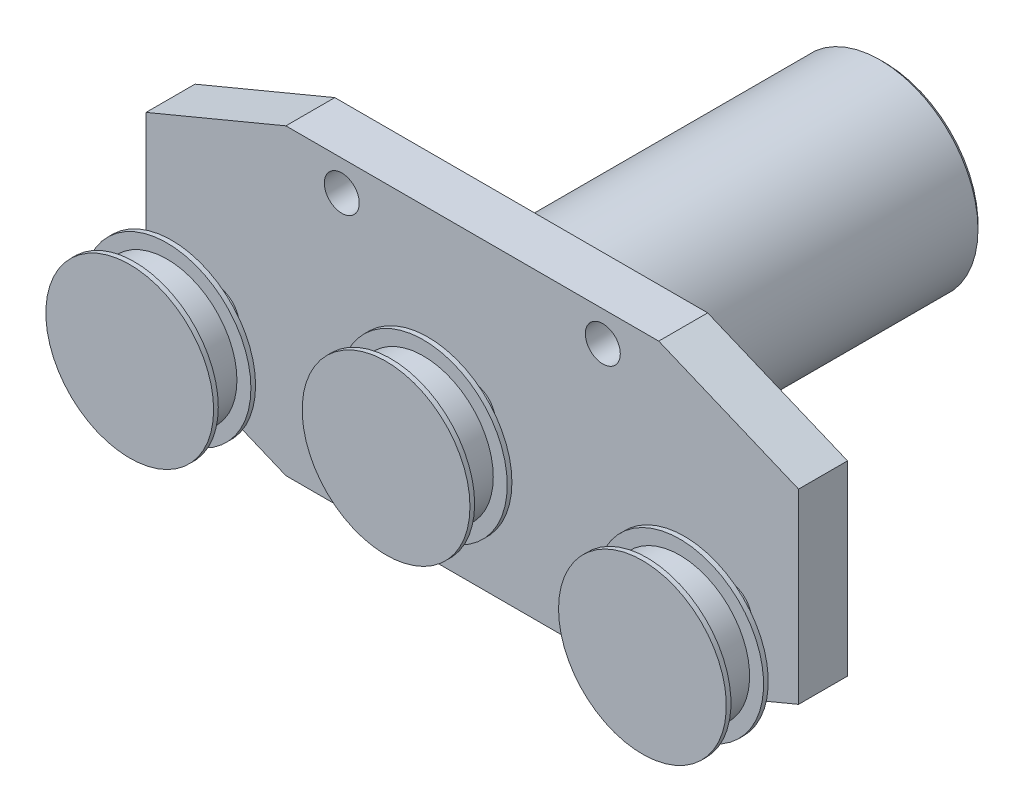
SolidWorks part; units mm, degrees
ref_plane "Front Plane" through (0, 0, 0) normal (0, 0, 1) x (1, 0, 0)
ref_plane "Top Plane" through (0, 0, 0) normal (0, 1, 0) x (1, 0, 0)
ref_plane "Right Plane" through (0, 0, 0) normal (1, 0, 0) x (0, 0, -1)
sketch "Sketch1" plane through (0, 0, 0) normal (0, 0, 1) x (1, 0, 0)
  line L0 (-20, 32.5) -> (-50, 20)
  line L1 (-20, 32.5) -> (20, 32.5)
  line L2 (-20, 32.5) -> (-20, -32.5)
  line L3 (-20, -32.5) -> (20, -32.5)
  line L4 (20, 32.5) -> (20, -32.5)
  line L5 (-20, 32.5) -> (20, -32.5) construction
  line L6 (-20, -32.5) -> (20, 32.5) construction
  line L7 (-50, 20) -> (-20, 20)
  line L8 (-50, 20) -> (-50, -20)
  line L9 (-50, -20) -> (-20, -20)
  line L10 (-20, 20) -> (-20, -20)
  line L11 (-50, 20) -> (-20, -20) construction
  line L12 (-50, -20) -> (-20, 20) construction
  line L13 (-50, -20) -> (-20, -32.5)
  line L14 (59.4, 0) -> (-59.4, 0) construction
  circle A0 centre (-8, 26) radius 2.25
  circle A1 centre (-8, -26) radius 2.25
  point P0 (0, 0)
  point P6 (-35, 0)
  dimension "D5" = 4.5
  dimension "D1" = 70
  dimension "D2" = 65
  dimension "D3" = 28
  dimension "D4" = 26
  dimension "D6" = 40
  dimension "D7" = 40
extrude "Boss-Extrude1" add sketch "Sketch1" along normal blind 10.5 contours L9 L13 L2 | L8 L9 L2 L7 | L0 L7 L2 | L4 L1 L2 L3 A0 A1 region at (-30, 24.1667, 0) region at (0.0991, 0, 0) region at (-35, 0, 0) region at (-30, -24.1667, 0)
mirror "Mirror1" about plane through (20, 0, 10.5) normal (1, 0, 0) of "Boss-Extrude1"
sketch "Sketch3" plane through (0, 0, 10.5) normal (0, 0, 1) x (1, 0, 0)
  line L0 (20, 32.5) -> (20, -32.5) construction
  line L1 (-20, 32.5) -> (60, 32.5) construction
  line L2 (-20, -32.5) -> (60, -32.5) construction
  line L4 (75, -9.5) -> (-35, -9.5) construction
  circle A0 centre (20, 0) radius 5
  circle A1 centre (-35, -9.5) radius 5
  circle A2 centre (75, -9.5) radius 5
  circle A3 centre (-35, -9.5) radius 18 construction
  circle A4 centre (75, -9.5) radius 18 construction
  dimension "D1" = 10
  dimension "D2" = 36
  dimension "D3" = 9.5
  dimension "D4" = 110
extrude "Boss-Extrude2" add sketch "Sketch3" along normal blind 9.5
sketch "Sketch4" plane through (0, 0, 10.5) normal (0, 0, 1) x (1, 0, 0)
  line L0 (59.4, 0) -> (-59.4, 0) construction
  line L1 (20, 32.5) -> (20, -31.5094) construction
  line L2 (-20, 32.5) -> (60, 32.5) construction
  circle A0 centre (-8, -26) radius 3.75
  circle A1 centre (-8, 26) radius 3.75
  circle A2 centre (48, 26) radius 3.75
  circle A3 centre (48, -26) radius 3.75
  dimension "D1" = 7.5
extrude "Cut-Extrude1" cut sketch "Sketch4" against normal blind 6
sketch "Sketch5" plane through (0, 0, 20) normal (0, 0, 1) x (1, 0, 0)
  circle A0 centre (20, 0) radius 18
  circle A1 centre (-35, -9.5) radius 18
  dimension "D1" = 36
extrude "Boss-Extrude3" add sketch "Sketch5" along normal blind 9
ref_plane "Plane1" through (0, 0, 28) normal (0, 0, 1) x (1, 0, 0)
sketch "Sketch7" plane through (0, 0, 28) normal (0, 0, 1) x (1, 0, 0)
  line L1 (-118.6146, 40.418) -> (48.6146, 40.418)
  line L2 (-118.6146, 40.418) -> (-118.6146, -59.418)
  line L3 (-118.6146, -59.418) -> (48.6146, -59.418)
  line L4 (48.6146, 40.418) -> (48.6146, -59.418)
  line L5 (-118.6146, 40.418) -> (48.6146, -59.418) construction
  line L6 (-118.6146, -59.418) -> (48.6146, 40.418) construction
  circle A0 centre (-35, -9.5) radius 15
  circle A1 centre (20, 0) radius 15
  dimension "D1" = 30
extrude "Cut-Extrude2" cut sketch "Sketch7" against normal blind 7
ref_plane "Plane2" through (20, 0, 0) normal (1, 0, 0) x (0, 0, -1)
mirror "Mirror2" about plane through (20, 0, 0) normal (1, 0, 0) of bodies 106
sketch "Sketch8" plane through (0, 0, 0) normal (0, 0, -1) x (-1, 0, 0)
  circle A0 centre (-20, 0) radius 21
  dimension "D1" = 42
extrude "Boss-Extrude4" add sketch "Sketch8" along normal blind 78
chamfer "Chamfer1" distance 1 angle 45 1 edges at (-1, 0, -78)
sketch "Sketch9" plane through (0, 0, 0) normal (0, 0, -1) x (-1, 0, 0)
  circle A0 centre (-75, -9.5) radius 2
  circle A1 centre (35, -9.5) radius 2
  dimension "D1" = 4
extrude "Boss-Extrude5" add sketch "Sketch9" along normal mid plane 6
